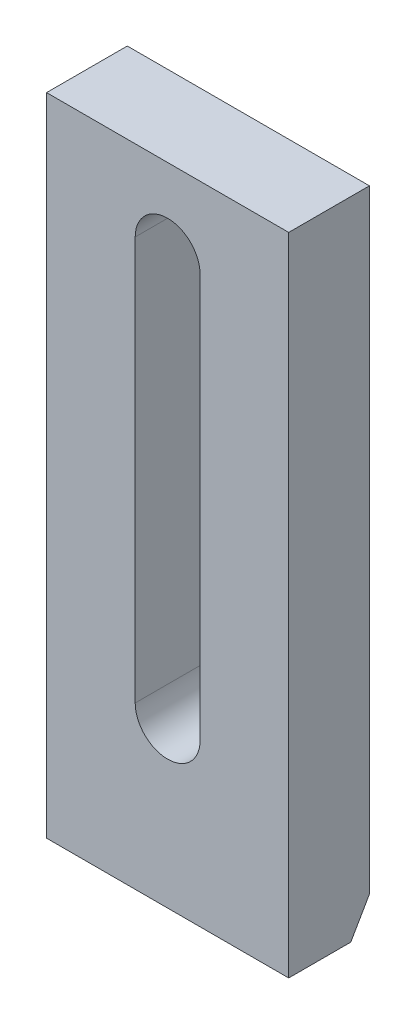
SolidWorks part; units mm, degrees
ref_plane "Спереди" through (0, 0, 0) normal (0, 0, 1) x (1, 0, 0)
ref_plane "Сверху" through (0, 0, 0) normal (0, 1, 0) x (1, 0, 0)
ref_plane "Справа" through (0, 0, 0) normal (1, 0, 0) x (0, 0, -1)
sketch "Эскиз1" plane through (0, 0, 0) normal (0, 0, 1) x (1, 0, 0)
  line L1 (0, 0) -> (75, 0)
  line L2 (0, 0) -> (0, 200)
  line L3 (0, 200) -> (75, 200)
  line L4 (75, 0) -> (75, 200)
  dimension "D1" = 75
  dimension "D2" = 200
extrude "Бобышка-Вытянуть1" add sketch "Эскиз1" along normal blind 25
sketch "Эскиз2" plane through (0, 0, 25) normal (0, 0, 1) x (1, 0, 0)
  line L1 (27.45, 50) -> (27.45, 175)
  line L2 (47.55, 50) -> (47.55, 175)
  line L3 (0, 200) -> (0, 0) construction
  line L4 (0, 0) -> (75, 0) construction
  arc A0 (27.45, 50) -> (47.55, 50) centre (37.5, 50) ccw
  arc A1 (27.45, 175) -> (47.55, 175) centre (37.5, 175) cw
  point P7 (27.45, 112.5)
  point P10 (47.55, 112.5)
  dimension "D1" = 37.5
  dimension "D2" = 50
extrude "Вырез-Вытянуть1" cut sketch "Эскиз2" against normal through all
chamfer "Фаска1" distance 10 angle 30 1 edges at (37.5, 0, 0) first distance on face at (37.5, 112.5, 0)
